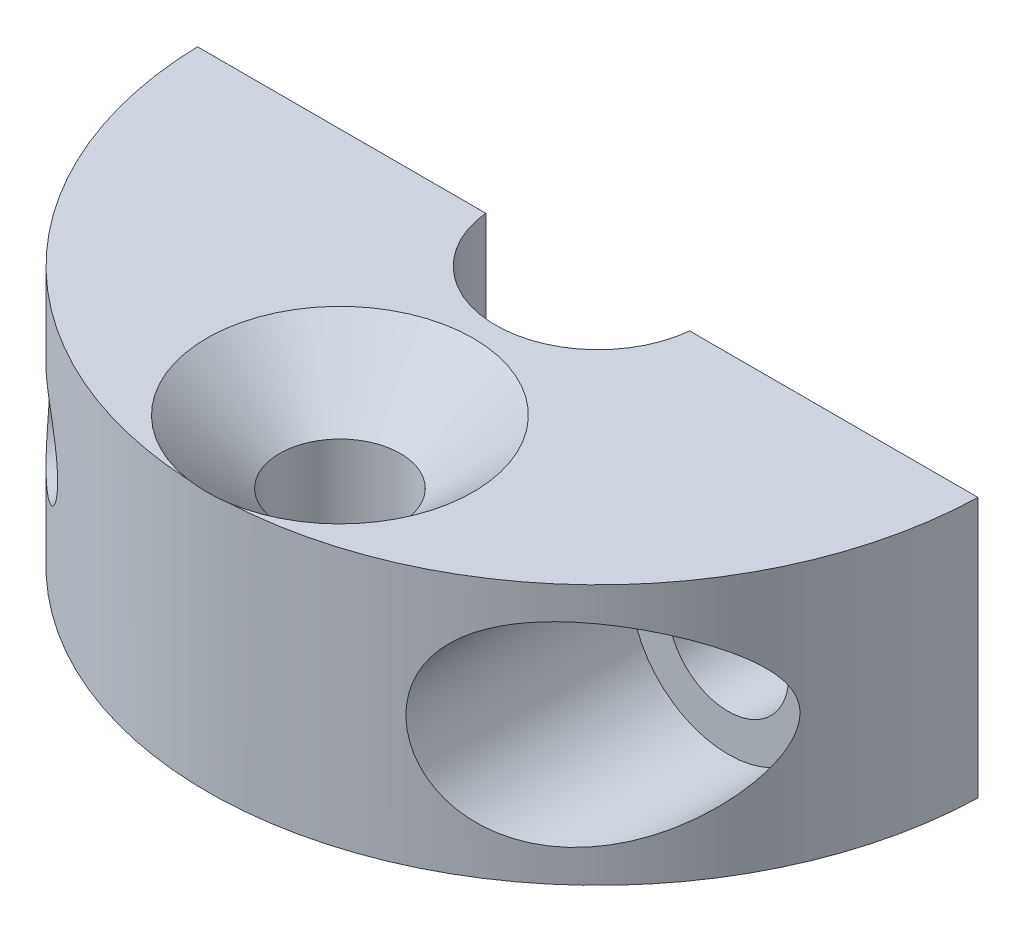
SolidWorks part; units mm, degrees
ref_plane "Front Plane" through (0, 0, 0) normal (0, 0, 1) x (1, 0, 0)
ref_plane "Top Plane" through (0, 0, 0) normal (0, 1, 0) x (1, 0, 0)
ref_plane "Right Plane" through (0, 0, 0) normal (1, 0, 0) x (0, 0, -1)
sketch "Sketch1" plane through (0, 0, 0) normal (0, 1, 0) x (1, 0, 0)
  line L0 (-9.5216, -0.254) -> (9.5216, -0.254)
  circle A0 centre (0, 0) radius 2.5
  circle A1 centre (0, 0) radius 9.525
  dimension "D1" = 5
  dimension "D2" = 19.05
  dimension "D3" = 0.254
extrude "Boss-Extrude1" add sketch "Sketch1" along normal blind 6.35 contours L0 A1 A0 region at (0, 0, 4.3775)
sketch "Sketch3" plane through (0, 0, 0.254) normal (0, 0, 1) x (1, 0, 0)
  line L0 (-9.5216, 0) -> (-2.4871, 0) construction
  circle A0 centre (-6.35, 3.175) radius 1.143
  dimension "D2" = 2.286
  dimension "D1" = 3.175
  dimension "D3" = 6.35
hole_wizard "#4-40 Tapped Hole1" positions "Sketch7" profile "Sketch6" tap size "#4-40" standard "ANSI Inch" end condition through all
sketch "Sketch7" plane through (0, 0, 0.254) normal (0, 0, -1) x (-1, 0, 0)
  point P0 (6.35, 3.175)
cosmetic thread "Hole Thread1" parameters "D2"=2.8448
sketch "Sketch6" plane through (-6.35, 3.175, 0.254) normal (1, 0, 0) x (0, 1, 0)
  line L0 (0, 0) -> (0, 9.271)
  line L1 (0, 9.271) -> (1.1303, 9.271)
  line L2 (1.1303, 9.271) -> (1.1303, 0)
  line L5 (1.1303, 0) -> (0, 0)
  line L11 (0, -6.35) -> (0, 107.95) construction
  dimension "Thru Tap Drill Dia." = 2.2606
  dimension "Thru Tap Drill Depth" = 9.271
ref_plane "Plane1" through (0, 0, 9.525) normal (0, 0, 1) x (1, 0, 0)
sketch "Sketch8" plane through (0, 0, 9.525) normal (0, 0, 1) x (1, 0, 0)
  circle A0 centre (6.35, 3.175) radius 2.3813
  dimension "D2" = 4.7625
  dimension "D1" = 6.35
extrude "Cut-Extrude1" cut sketch "Sketch8" against normal blind 6.35
sketch "Sketch9" plane through (0, 0, 3.175) normal (0, 0, 1) x (1, 0, 0)
  circle A0 centre (6.35, 3.175) radius 1.4732
  dimension "D1" = 2.9464
extrude "Cut-Extrude2" cut sketch "Sketch9" against normal through all
sketch "Sketch10" plane through (0, 6.35, 0) normal (0, 1, 0) x (1, 0, 0)
  circle A0 centre (0, -6.2992) radius 1.4732
  dimension "D2" = 2.9464
  dimension "D1" = 6.2992
extrude "Cut-Extrude3" cut sketch "Sketch10" against normal through all
chamfer "Chamfer1" distance 1.778 angle 41 1 edges at (0, 6.35, 7.7724) first distance on face at (0, 6.35, 7.7724)
